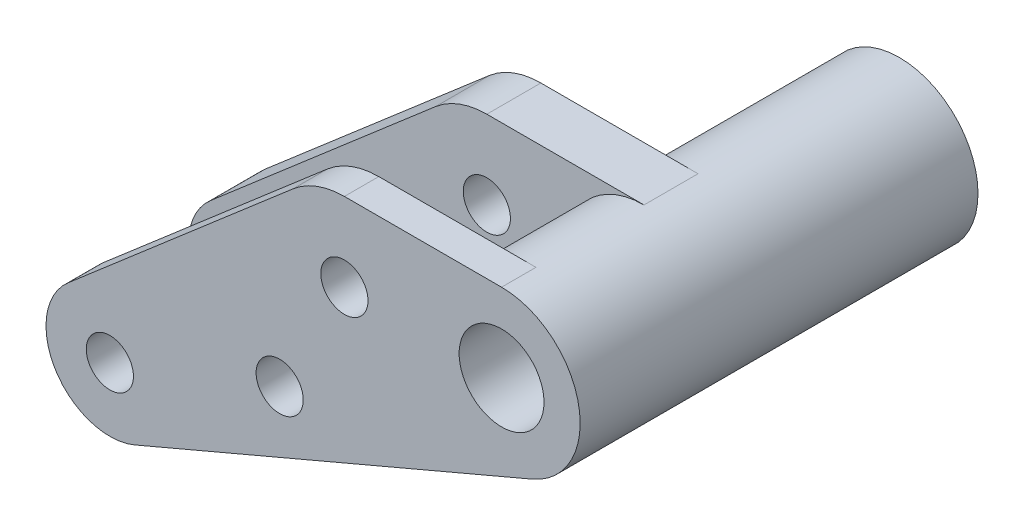
SolidWorks part; units mm, degrees
ref_plane "Front Plane" through (0, 0, 0) normal (0, 0, 1) x (1, 0, 0)
ref_plane "Top Plane" through (0, 0, 0) normal (0, 1, 0) x (1, 0, 0)
ref_plane "Right Plane" through (0, 0, 0) normal (1, 0, 0) x (0, 0, -1)
sketch "Sketch1" plane through (0, 0, 0) normal (0, 0, 1) x (1, 0, 0)
  line L0 (-12.7, 0) -> (0, 0) construction
  line L3 (-31.6528, -14.7599) -> (0, 0) construction
  line L6 (-29.633, -19.5075) -> (2.4859, -5.8432)
  line L7 (0, 0) -> (-31.6528, -14.7599) construction
  line L8 (-35.0207, -10.8515) -> (-16.8451, 4.8104)
  line L9 (-12.7, 6.35) -> (0, 6.35)
  arc A0 (2.4859, -5.8432) -> (0, 6.35) centre (0, 0) ccw
  arc A3 (-35.0207, -10.8515) -> (-29.633, -19.5075) centre (-31.6528, -14.7599) ccw
  circle A4 centre (-12.7, 0) radius 1.905
  circle A5 centre (-31.6528, -14.7599) radius 1.905
  circle A6 centre (0, 0) radius 3.429
  arc A8 (-12.7, 6.35) -> (-16.8451, 4.8104) centre (-12.7, 0) ccw
  dimension "D3" = 3.81
  dimension "D4" = 10.3187
  dimension "D5" = 6.35
  dimension "D6" = 6.35
  dimension "D8" = 3.81
  dimension "D9" = 6.858
  dimension "D1" = 12.7
  dimension "D2" = 34.925
  dimension "D7" = 25
extrude "Boss-Extrude1" add sketch "Sketch1" against normal blind 15.875
sketch "Sketch5" plane through (0, 0, 0) normal (0, 0, 1) x (1, 0, 0)
  line L0 (-16.8451, 4.8104) -> (-35.0207, -10.8515) construction
  line L1 (-29.633, -19.5075) -> (2.4859, -5.8432) construction
  line L2 (-26.4934, -3.5035) -> (-35.0207, -10.8515)
  line L3 (-29.633, -19.5075) -> (-26.4934, -18.1719)
  line L4 (-26.4934, -18.1719) -> (-26.4934, -3.5035)
  arc A0 (-35.0207, -10.8515) -> (-29.633, -19.5075) centre (-31.6528, -14.7599) ccw construction
  arc A1 (-35.0207, -10.8515) -> (-29.633, -19.5075) centre (-31.6528, -14.7599) ccw
  circle A2 centre (-31.6528, -14.7599) radius 5.1594 construction
extrude "Cut-Extrude3" [suppressed] cut sketch "Sketch5" against normal blind 9.525
ref_plane "Plane1" through (0, 0, -7.1437) normal (0, 0, 1) x (1, 0, 0)
sketch "Sketch4" plane through (0, 0, -7.1437) normal (0, 0, 1) x (1, 0, 0)
  line L7 (0, 6.35) -> (-12.7, 6.35) construction
  line L8 (-16.8451, 4.8104) -> (-35.0207, -10.8515) construction
  line L10 (0, 6.35) -> (-12.7, 6.35)
  line L11 (-16.8451, 4.8104) -> (-35.0207, -10.8515)
  line L12 (-15.074, -5.8895) -> (-20.2858, -3.7888)
  line L14 (-27.0539, -17.0985) -> (-20.2858, -3.7888)
  line L15 (-29.633, -19.5075) -> (2.4859, -5.8432) construction
  arc A8 (-35.0207, -10.8515) -> (-29.633, -19.5075) centre (-31.6528, -14.7599) ccw construction
  arc A12 (-35.0207, -10.8515) -> (-29.633, -19.5075) centre (-31.6528, -14.7599) ccw
  arc A13 (0, 6.35) -> (-6.35, 0) centre (0, 0) ccw
  arc A16 (-15.074, -5.8895) -> (-6.35, 0) centre (-12.7, 0) ccw
  arc A17 (-12.7, 6.35) -> (-16.8451, 4.8104) centre (-12.7, 0) ccw construction
  arc A18 (-12.7, 6.35) -> (-16.8451, 4.8104) centre (-12.7, 0) ccw
  arc A19 (-29.633, -19.5075) -> (-27.0539, -17.0985) centre (-31.6528, -14.7599) ccw
  dimension "D1" = 6.35
  dimension "D2" = 40
  dimension "D3" = 95
extrude "Cut-Extrude2" cut sketch "Sketch4" against normal mid plane 8.7312
sketch "Sketch6" plane through (0, 0, -15.875) normal (0, 0, -1) x (-1, 0, 0)
  circle A0 centre (0, 0) radius 6.35
  circle A1 centre (0, 0) radius 3.429 construction
  circle A2 centre (0, 0) radius 3.429
  arc A3 (0, 6.35) -> (-2.4859, -5.8432) centre (0, 0) ccw construction
extrude "Boss-Extrude2" add sketch "Sketch6" along normal offset from surface (16.2719 mm away) 32.1469 up to face at (3.429, 0, 0)
sketch "Sketch7" plane through (0, 0, -15.875) normal (0, 0, -1) x (-1, 0, 0)
  line L0 (29.633, -19.5075) -> (-2.4859, -5.8432) construction
  circle A0 centre (17.9305, -9.5604) radius 1.905
  dimension "D1" = 3.81
  dimension "D2" = 4.572
  dimension "D3" = 20.32
extrude "Cut-Extrude4" cut sketch "Sketch7" against normal through all
sketch "Sketch8" plane through (0, 0, -15.875) normal (0, 0, -1) x (-1, 0, 0)
  circle A0 centre (17.9305, -9.5604) radius 2.286
  dimension "D1" = 4.572
extrude "Cut-Extrude5" cut sketch "Sketch8" against normal up to surface (4.3656 mm away) up to face at (-18.4827, -4.7545, -11.5094)
